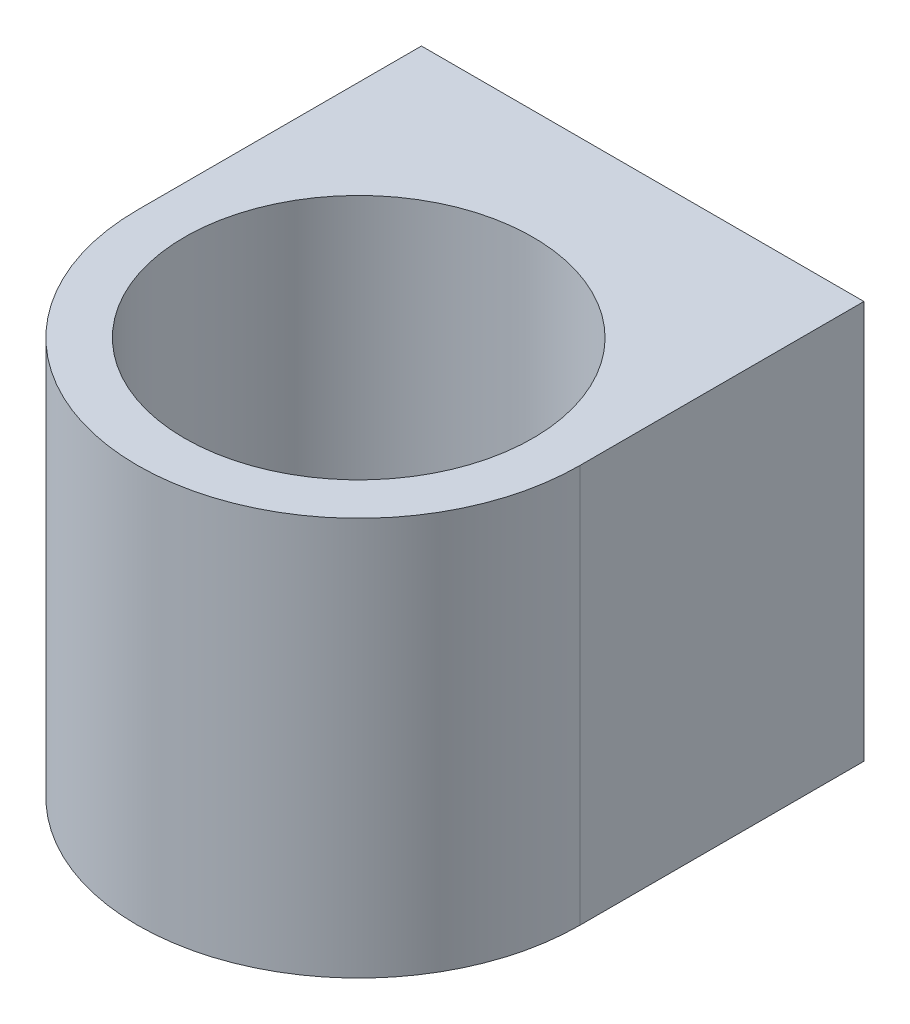
SolidWorks part; units mm, degrees
material "6061-T6 (SS)"
ref_plane "Front Plane" through (0, 0, 0) normal (0, 0, 1) x (1, 0, 0)
ref_plane "Top Plane" through (0, 0, 0) normal (0, 1, 0) x (1, 0, 0)
ref_plane "Right Plane" through (0, 0, 0) normal (1, 0, 0) x (0, 0, -1)
sketch "Sketch1" plane through (0, 0, 0) normal (0, 1, 0) x (1, 0, 0)
  line L0 (-14.1125, 0) -> (-14.1125, 14.1125)
  line L2 (14.1125, 14.1125) -> (14.1125, 0)
  line L3 (-14.1125, 14.1125) -> (-14.1125, 18.1125)
  line L4 (-14.1125, 18.1125) -> (14.1125, 18.1125)
  line L5 (14.1125, 18.1125) -> (14.1125, 14.1125)
  circle A0 centre (0, 0) radius 11.1125
  arc A1 (-14.1125, 0) -> (14.1125, 0) centre (0, 0) ccw
  circle A2 centre (0, 0) radius 14.1125 construction
  dimension "D1" = 22.225
  dimension "D2" = 3
extrude "Boss-Extrude1" add sketch "Sketch1" along normal blind 12.7 and the other way blind 12.7
sketch "Sketch2" plane through (0, 0, -18.1125) normal (0, 0, -1) x (-1, 0, 0)
  line L0 (-14.1125, 12.7) -> (-8.1125, 12.7) construction
  line L1 (-14.1125, 12.7) -> (14.1125, 12.7) construction
  line L2 (-8.1125, 12.7) -> (-8.1125, 6.7) construction
  line L3 (14.1125, 12.7) -> (8.1125, 12.7) construction
  line L4 (8.1125, 12.7) -> (8.1125, 6.7) construction
  line L5 (-14.1125, -12.7) -> (-8.1125, -12.7) construction
  line L6 (-14.1125, -12.7) -> (14.1125, -12.7) construction
  line L7 (-8.1125, -12.7) -> (-8.1125, -6.7) construction
  line L8 (14.1125, -12.7) -> (8.1125, -12.7) construction
  line L9 (8.1125, -12.7) -> (8.1125, -6.7) construction
  circle A0 centre (8.1125, -6.7) radius 3
  circle A1 centre (-8.1125, -6.7) radius 3
  circle A2 centre (-8.1125, 6.7) radius 3
  circle A3 centre (8.1125, 6.7) radius 3
extrude "Cut-Extrude1" cut sketch "Sketch2" against normal blind 7
